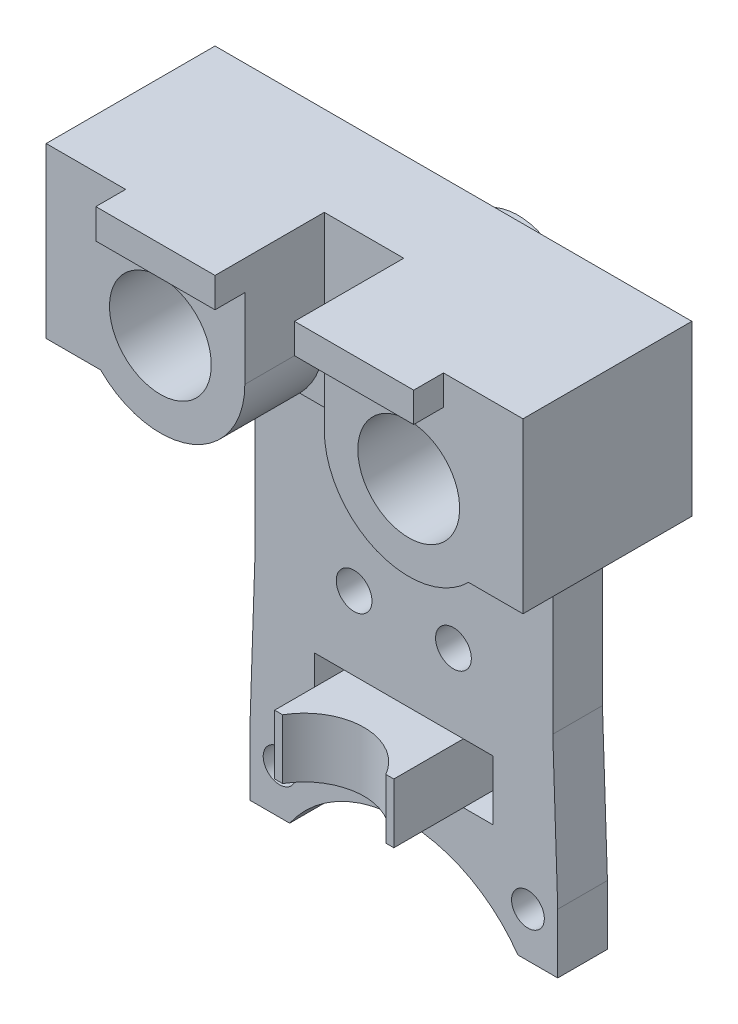
SolidWorks part; units mm, degrees
ref_plane "Front Plane" through (0, 0, 0) normal (0, 0, 1) x (1, 0, 0)
ref_plane "Top Plane" through (0, 0, 0) normal (0, 1, 0) x (1, 0, 0)
ref_plane "Right Plane" through (0, 0, 0) normal (1, 0, 0) x (0, 0, -1)
sketch "Sketch1" plane through (0, 0, 0) normal (0, 0, 1) x (1, 0, 0)
  line L0 (-15, -21) -> (-15.5, -36)
  line L1 (-15, -42) -> (15, -42)
  line L2 (-15, -42) -> (-15, 0)
  line L3 (-15, 0) -> (15, 0)
  line L4 (15, -42) -> (15, 0)
  line L5 (0, 0) -> (0, -42) construction
  line L6 (-15, -21) -> (15, -21) construction
  line L7 (-15.5, -36) -> (-15.5, -42)
  line L8 (-15.5, -42) -> (-15, -42)
  line L9 (15, -21) -> (15.5, -36)
  line L10 (15.5, -36) -> (15.5, -42)
  line L11 (15.5, -42) -> (15, -42)
  point P224 (0, -21)
  dimension "D1" = 30
  dimension "D2" = 42
  dimension "D3" = 31
  dimension "D4" = 6
extrude "Boss-Extrude1" add sketch "Sketch1" against normal blind 5 contours L1 L4 L3 L2 | L7 L8 L2 L0 | L11 L10 L9 L4 region at (-15.2037, -34.5556, 0) region at (0, -21, 0) region at (15.2037, -34.5556, 0)
hole_wizard "M3 Clearance Hole1" positions "Sketch2" profile "Sketch3" hole size "M3" standard "ANSI Metric" end condition through all
sketch "Sketch2" plane through (0, 0, 0) normal (0, 0, 1) x (1, 0, 0)
  line L1 (-5, -3.5) -> (5, -3.5)
  line L2 (-5, -3.5) -> (-5, -18.5)
  line L3 (-5, -18.5) -> (5, -18.5)
  line L4 (5, -3.5) -> (5, -18.5)
  line L5 (0, -3.5) -> (0, 0) construction
  line L7 (-5, -11) -> (5, -11) construction
  point P0 (-5, -3.5)
  point P2 (5, -3.5)
  point P4 (-5, -18.5)
  point P6 (5, -18.5)
  dimension "D1" = 15
  dimension "D2" = 10
  dimension "D3" = 11
sketch "Sketch3" plane through (-5, -3.5, 0) normal (1, 0, 0) x (0, -1, 0)
  line L0 (0, 0) -> (0, 5)
  line L1 (0, 5) -> (1.8, 5)
  line L2 (1.8, 5) -> (1.8, 0)
  line L5 (1.8, 0) -> (0, 0)
  line L11 (0, -6.35) -> (0, 107.95) construction
  dimension "Thru Hole Dia." = 3.6
  dimension "Thru Hole Depth" = 5
sketch "Sketch4" plane through (0, 0, 0) normal (0, 0, 1) x (1, 0, 0)
  line L0 (0, -50) -> (0, 0) construction
  circle A0 centre (0, -50) radius 14
  dimension "D2" = 28
  dimension "D1" = 50
extrude "Cut-Extrude1" cut sketch "Sketch4" against normal blind 5
hole_wizard "M4x0.7 Tapped Hole1" positions "Sketch6" profile "Sketch7" tap size "M4x0.7" standard "ANSI Metric" end condition through all
sketch "Sketch6" plane through (0, 0, 0) normal (0, 0, 1) x (1, 0, 0)
  line L0 (-12.5, -37.5) -> (12.5, -37.5) construction
  line L2 (0, -37.5) -> (0, 0) construction
  arc A0 (11.4891, -42) -> (-11.4891, -42) centre (0, -50) ccw construction
  point P2 (-12.5, -37.5)
  point P4 (12.5, -37.5)
  dimension "D1" = 12.5
  dimension "D2" = 25
sketch "Sketch7" plane through (-12.5, -37.5, 0) normal (1, 0, 0) x (0, -1, 0)
  line L0 (0, 0) -> (0, 5)
  line L1 (0, 5) -> (1.65, 5)
  line L2 (1.65, 5) -> (1.65, 0)
  line L5 (1.65, 0) -> (0, 0)
  line L11 (0, -6.35) -> (0, 107.95) construction
  dimension "Thru Tap Drill Dia." = 3.3
  dimension "Thru Tap Drill Depth" = 5
cosmetic thread "Hole Thread1" parameters "D2"=4
cosmetic thread "Hole Thread2" parameters "D2"=4
sketch "Sketch8" plane through (0, 0, 0) normal (0, 0, 1) x (1, 0, 0)
  line L0 (-15, 0) -> (15, 0) construction
  line L1 (-6, -31.9) -> (6, -31.9)
  line L2 (-6, -31.9) -> (-6, -25.9)
  line L3 (-6, -25.9) -> (6, -25.9)
  line L4 (6, -31.9) -> (6, -25.9)
  line L5 (0, -25.9) -> (0, -31.9) construction
  line L6 (-6, -28.9) -> (6, -28.9) construction
  point P0 (0, -28.9)
  dimension "D1" = 6
  dimension "D2" = 25.9
  dimension "D3" = 12
extrude "Boss-Extrude2" add sketch "Sketch8" along normal blind 7
sketch "Sketch9" plane through (0, -25.9, 0) normal (0, 1, 0) x (1, 0, 0)
  line L0 (0, -10) -> (0, 0) construction
  circle A0 centre (0, -10) radius 6
  dimension "D1" = 12
  dimension "D2" = 10
extrude "Cut-Extrude2" cut sketch "Sketch9" against normal blind 10
sketch "Sketch13" plane through (0, 0, 0) normal (0, 0, 1) x (1, 0, 0)
  line L1 (-6, -31.9) -> (-9, -31.9)
  line L2 (-6, -31.9) -> (-6, -25.9)
  line L3 (-6, -25.9) -> (-9, -25.9)
  line L4 (-9, -31.9) -> (-9, -25.9)
  line L5 (-7.5, -25.9) -> (-7.5, -31.9) construction
  line L6 (-6, -28.9) -> (-9, -28.9) construction
  line L7 (6, -31.9) -> (9, -31.9)
  line L8 (6, -31.9) -> (6, -25.9)
  line L9 (6, -25.9) -> (9, -25.9)
  line L10 (9, -31.9) -> (9, -25.9)
  line L11 (7.5, -25.9) -> (7.5, -31.9) construction
  line L12 (6, -28.9) -> (9, -28.9) construction
  point P92 (-7.5, -28.9)
  point P122 (7.5, -28.9)
  dimension "D1" = 3
extrude "Cut-Extrude4" cut sketch "Sketch13" against normal blind 6
sketch "Sketch10" plane through (0, 0, 0) normal (0, 0, 1) x (1, 0, 0)
  line L1 (-15, 0) -> (15, 0)
  line L2 (-15, 0) -> (-15, 5.35)
  line L3 (-15, 5.35) -> (15, 5.35)
  line L4 (15, 0) -> (15, 5.35)
  line L5 (0, 5.35) -> (0, 0) construction
  line L6 (-15, 2.675) -> (15, 2.675) construction
  point P196 (0, 2.675)
  dimension "D1" = 5.35
extrude "Boss-Extrude3" [suppressed] add sketch "Sketch10" against normal up to surface and the other way blind 8 up to face at (-7.5, -28.9, -5)
sketch "Sketch12" [suppressed] plane through (0, 5.35, 0) normal (0, 1, 0) x (1, 0, 0)
  line L0 (-11, -4) -> (-15, -4) construction
  line L1 (-4, -4.25) -> (-15, -4.25) construction
  line L2 (-15, -8) -> (-15, 5) construction
  line L3 (-9.0112, -2.2111) -> (-8.4888, 2.7111) construction
  line L4 (-2, -2.25) -> (-2, 2.5) construction
  line L5 (0, 0) -> (0, 2.5) construction
  line L6 (0, 5) -> (0, -8) construction
  line L7 (-15, 5) -> (15, 5) construction
  line L8 (15, -8) -> (-15, -8) construction
  line L9 (0, 2.5) -> (-6.5, 2.5) construction
  circle A0 centre (-11, -2) radius 2
  circle A1 centre (-4, -2.25) radius 2
  circle A2 centre (-6.5, 2.5) radius 1.75
  circle A3 centre (0, 2.5) radius 1.75
  circle A4 centre (-6.5, 2.5) radius 2 construction
  circle A5 centre (0, 2.5) radius 2 construction
  circle A6 centre (11, -2) radius 2
  circle A7 centre (4, -2.25) radius 2
  circle A8 centre (6.5, 2.5) radius 1.75
  dimension "D1" = 4
  dimension "D4" = 3.5
  dimension "D9" = 4
  dimension "D2" = 4
  dimension "D3" = 0.25
  dimension "D5" = 4
  dimension "D6" = 11
  dimension "D7" = 2.5
  dimension "D8" = 6.5
extrude "Cut-Extrude3" [suppressed] cut sketch "Sketch12" against normal blind 6
sketch "Sketch14" plane through (0, 0, 0) normal (0, 0, 1) x (1, 0, 0)
  line L1 (-24, 0) -> (24, 0)
  line L2 (-24, 0) -> (-24, 17)
  line L3 (-24, 17) -> (24, 17)
  line L4 (24, 0) -> (24, 17)
  line L5 (0, 17) -> (0, 0) construction
  line L6 (-24, 8.5) -> (24, 8.5) construction
  point P4 (18.5344, -1.4982)
  point P5 (0, 0)
  point P120 (0, 8.5)
  dimension "D1" = 17
  dimension "D2" = 48
extrude "Boss-Extrude5" add sketch "Sketch14" against normal up to surface (5 mm away) and the other way blind 12 up to face at (-7.5, -28.9, -5)
sketch "Sketch15" plane through (0, 0, -5) normal (0, 0, -1) x (-1, 0, 0)
  line L0 (-12.5, 6) -> (12.5, 6) construction
  line L3 (0, 6) -> (0, 0) construction
  circle A6 centre (12.5, 6) radius 5.125
  circle A7 centre (-12.5, 6) radius 5.125
  dimension "D2" = 25
  dimension "D3" = 10.25
  dimension "D1" = 6
extrude "Cut-Extrude5" cut sketch "Sketch15" against normal through all
sketch "Sketch16" plane through (0, 0, 12) normal (0, 0, 1) x (1, 0, 0)
  circle A0 centre (-12.5, 6) radius 8.5
  circle A1 centre (12.5, 6) radius 8.5
  circle A2 centre (12.5, 6) radius 5.125 construction
  circle A3 centre (-12.5, 6) radius 5.125 construction
  circle A4 centre (12.5, 6) radius 5.125
  circle A5 centre (-12.5, 6) radius 5.125
  dimension "D1" = 17
extrude "Boss-Extrude6" add sketch "Sketch16" against normal up to surface (17 mm away) up to face at (-17.625, 6, -5)
sketch "Sketch18" plane through (0, 0, -5) normal (0, 0, -1) x (-1, 0, 0)
  line L0 (0, 5.25) -> (0, 0) construction
  circle A0 centre (0, 5.25) radius 1.75
  circle A1 centre (0, 5.25) radius 5.75
  dimension "D1" = 3.5
  dimension "D2" = 3.5
  dimension "D3" = 4
extrude "Boss-Extrude7" add sketch "Sketch18" along normal blind 6.5 separate body
sketch "Sketch19" plane through (0, 0, -5) normal (0, 0, -1) x (-1, 0, 0)
  circle A0 centre (0, 5.25) radius 1.75 construction
  circle A1 centre (0, 5.25) radius 1.75
extrude "Cut-Extrude6" cut sketch "Sketch19" against normal up to surface (17 mm away) up to face at (0, 3.625, 12)
sketch "Sketch20" plane through (0, 0, 12) normal (0, 0, 1) x (1, 0, 0)
  line L0 (24, 17) -> (-24, 17) construction
  line L1 (-16, 17) -> (16, 17)
  line L2 (-16, 17) -> (-16, 14)
  line L3 (-16, 14) -> (16, 14)
  line L4 (16, 17) -> (16, 14)
  line L5 (0, 14) -> (0, 17) construction
  line L6 (-16, 15.5) -> (16, 15.5) construction
  line L7 (0, 0) -> (0, 14) construction
  point P232 (0, 15.5)
  dimension "D1" = 3
  dimension "D2" = 32
extrude "Boss-Extrude8" add sketch "Sketch20" along normal blind 3
sketch "Sketch22" plane through (0, 0, 12) normal (0, 0, 1) x (1, 0, 0)
  line L0 (-6.4792, 0) -> (6.4792, 0) construction
  line L1 (-4, 0) -> (4, 0)
  line L2 (-4, 0) -> (-4, 17)
  line L3 (-4, 17) -> (4, 17)
  line L4 (4, 0) -> (4, 17)
  line L5 (0, 17) -> (0, 0) construction
  line L6 (-4, 8.5) -> (4, 8.5) construction
  line L7 (16, 17) -> (-16, 17) construction
  line L8 (6.4792, 0) -> (4, 0)
  line L9 (-4, 0) -> (-6.4792, 0)
  arc A0 (-6.4792, 0) -> (-4, 6) centre (-12.5, 6) ccw
  arc A4 (6.4792, 0) -> (4, 6) centre (12.5, 6) cw
  circle A5 centre (12.5, 6) radius 5.125 construction
  circle A6 centre (-12.5, 6) radius 5.125 construction
  point P300 (0, 8.5)
  circle M4 centre (0, 5.25) radius 1.75
  line M10 (-6.4792, 0) -> (6.4792, 0)
  line M16 (16, 14) -> (-16, 14)
  dimension "D1" = 8
extrude "Cut-Extrude7" cut sketch "Sketch22" against normal blind 8 and the other way blind 8 contours L4 L2 M10 M16 M4 | A0 L2 M10 | A4 L4 M10 | L4 L3 L2 M16 region at (0, 7.1645, 12) region at (-4.7206, 1.4527, 12) region at (4.7206, 1.4527, 12) region at (0, 15.5, 12)
